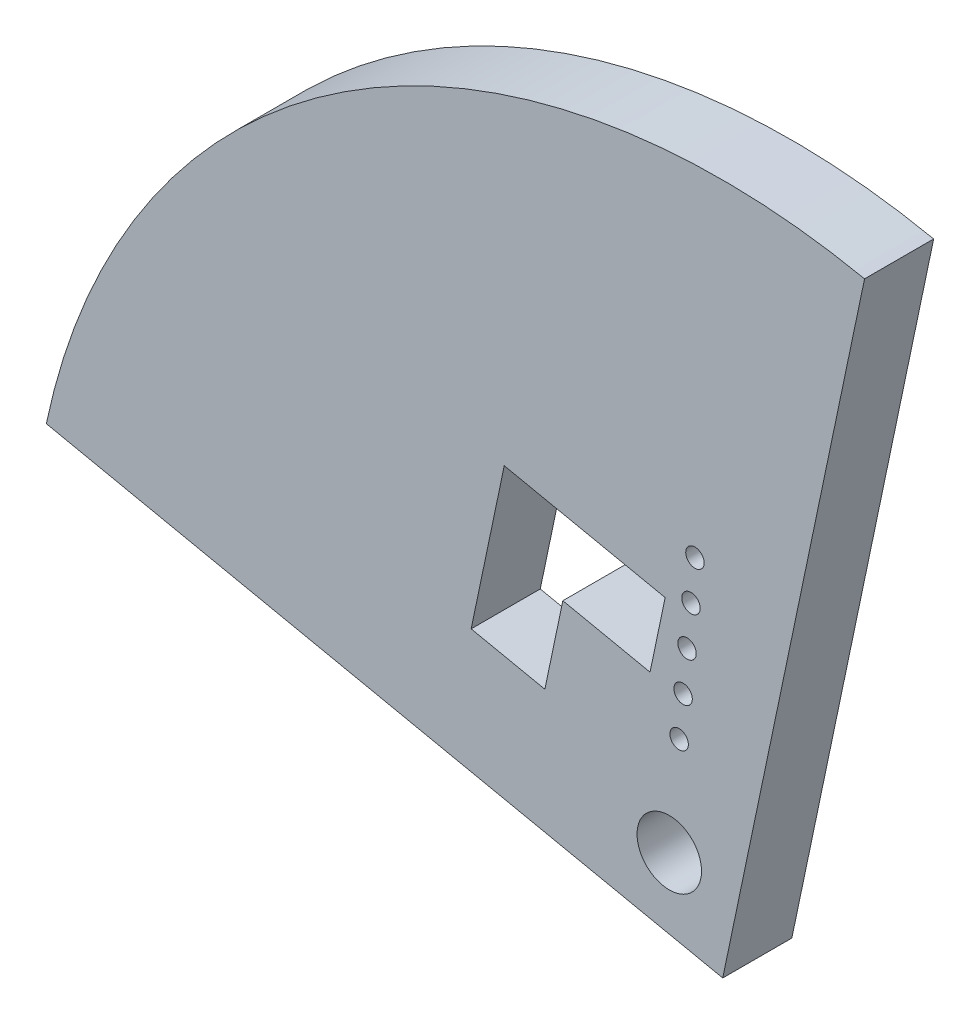
SolidWorks part; units mm, degrees
ref_plane "Front Plane" through (0, 0, 0) normal (0, 0, 1) x (1, 0, 0)
ref_plane "Top Plane" through (0, 0, 0) normal (0, 1, 0) x (1, 0, 0)
ref_plane "Right Plane" through (0, 0, 0) normal (1, 0, 0) x (0, 0, -1)
sketch "Sketch2" plane through (0, 0, 0) normal (0, 0, 1) x (1, 0, 0)
  line L0 (-11.2209, 59.4953) -> (-19.0396, 22.2062)
  line L1 (-19.0396, 22.2062) -> (-56.3287, 30.0249)
  arc A0 (-11.2209, 59.4953) -> (-56.3287, 30.0249) centre (-19.0396, 22.2062) ccw
extrude "Boss-Extrude2" add sketch "Sketch2" along normal blind 3.81
sketch "Sketch3" plane through (0, 0, 3.81) normal (0, 0, 1) x (1, 0, 0)
  line L0 (-19.0396, 22.2062) -> (-11.2209, 59.4953) construction
  line L1 (-56.3287, 30.0249) -> (-19.0396, 22.2062) construction
  circle A0 centre (-21.9866, 26.717) radius 1.778
  dimension "D1" = 3.81
  dimension "D2" = 3.81
extrude "Cut-Extrude1" cut sketch "Sketch3" against normal through all
sketch "Sketch4" plane through (0, 0, 0) normal (0, 0, -1) x (-1, 0, 0)
  line L0 (19.0396, 22.2062) -> (15.8441, 37.4462) construction
  line L2 (19.0396, 22.2062) -> (11.2209, 59.4953) construction
  line L3 (15.8441, 37.4462) -> (31.0841, 40.6417) construction
  line L4 (31.0841, 40.6417) -> (34.2796, 25.4017) construction
  line L5 (56.3287, 30.0249) -> (19.0396, 22.2062) construction
  line L6 (31.0841, 40.6417) -> (31.9181, 36.6642)
  line L7 (31.0841, 40.6417) -> (22.213, 38.7816)
  line L8 (31.9181, 36.6642) -> (23.047, 34.8041)
  line L9 (22.213, 38.7816) -> (23.047, 34.8041)
  line L10 (27.8541, 35.8121) -> (28.8444, 31.0888)
  line L11 (27.8541, 35.8121) -> (31.9181, 36.6642)
  line L12 (28.8444, 31.0888) -> (32.9084, 31.9409)
  line L13 (31.9181, 36.6642) -> (32.9084, 31.9409)
  dimension "D1" = 15.24
  dimension "D2" = 15.24
  dimension "D3" = 4.064
  dimension "D4" = 0
  dimension "D5" = 4.064
  dimension "D6" = 8.8711
  dimension "D7" = 8.89
extrude "Cut-Extrude2" cut sketch "Sketch4" against normal through all contours L7 L9 L8 L6 | L13 L8 L10 L12 region at (-27.0655, 37.7229, 0) region at (-30.3812, 33.8765, 0)
sketch "Sketch5" plane through (0, 0, 0) normal (0, 0, -1) x (-1, 0, 0)
  line L2 (19.0396, 22.2062) -> (56.3287, 30.0249)
  line L3 (11.2209, 59.4953) -> (19.0396, 22.2062)
  line L4 (19.0396, 22.2062) -> (56.3287, 30.0249)
  line L5 (11.2209, 59.4953) -> (19.0396, 22.2062)
  line L6 (19.0396, 22.2062) -> (56.3287, 30.0249)
  line L7 (11.2209, 59.4953) -> (19.0396, 22.2062)
  line L8 (19.0396, 22.2062) -> (56.3287, 30.0249)
  line L9 (11.2209, 59.4953) -> (19.0396, 22.2062)
  circle A0 centre (21.4425, 32.406) radius 0.508 construction
  arc A1 (56.3287, 30.0249) -> (11.2209, 59.4953) centre (19.0396, 22.2062) ccw
  arc A2 (56.3287, 30.0249) -> (11.2209, 59.4953) centre (19.0396, 22.2062) ccw
  arc A3 (56.3287, 30.0249) -> (11.2209, 59.4953) centre (19.0396, 22.2062) ccw
  arc A4 (56.3287, 30.0249) -> (11.2209, 59.4953) centre (19.0396, 22.2062) ccw
  circle A5 centre (21.2249, 34.6817) radius 0.508 construction
  circle A6 centre (21.0073, 36.9573) radius 0.508 construction
  circle A7 centre (20.5721, 41.5085) radius 0.508 construction
  circle A8 centre (20.7897, 39.2329) radius 0.508 construction
  circle A9 centre (21.4425, 32.406) radius 0.508
  circle A10 centre (21.2249, 34.6817) radius 0.508
  circle A11 centre (21.0073, 36.9573) radius 0.508
  circle A12 centre (20.5721, 41.5085) radius 0.508
  circle A13 centre (20.7897, 39.2329) radius 0.508
  dimension "D1" = 0
  dimension "D2" = 0
extrude "Cut-Extrude3" cut sketch "Sketch5" against normal through all contours A11 | A9 | A10 | A13 | A12 region at (-21.4425, 32.406, 0) region at (-21.2249, 34.6817, 0) region at (-21.0073, 36.9573, 0) region at (-20.7897, 39.2329, 0)
